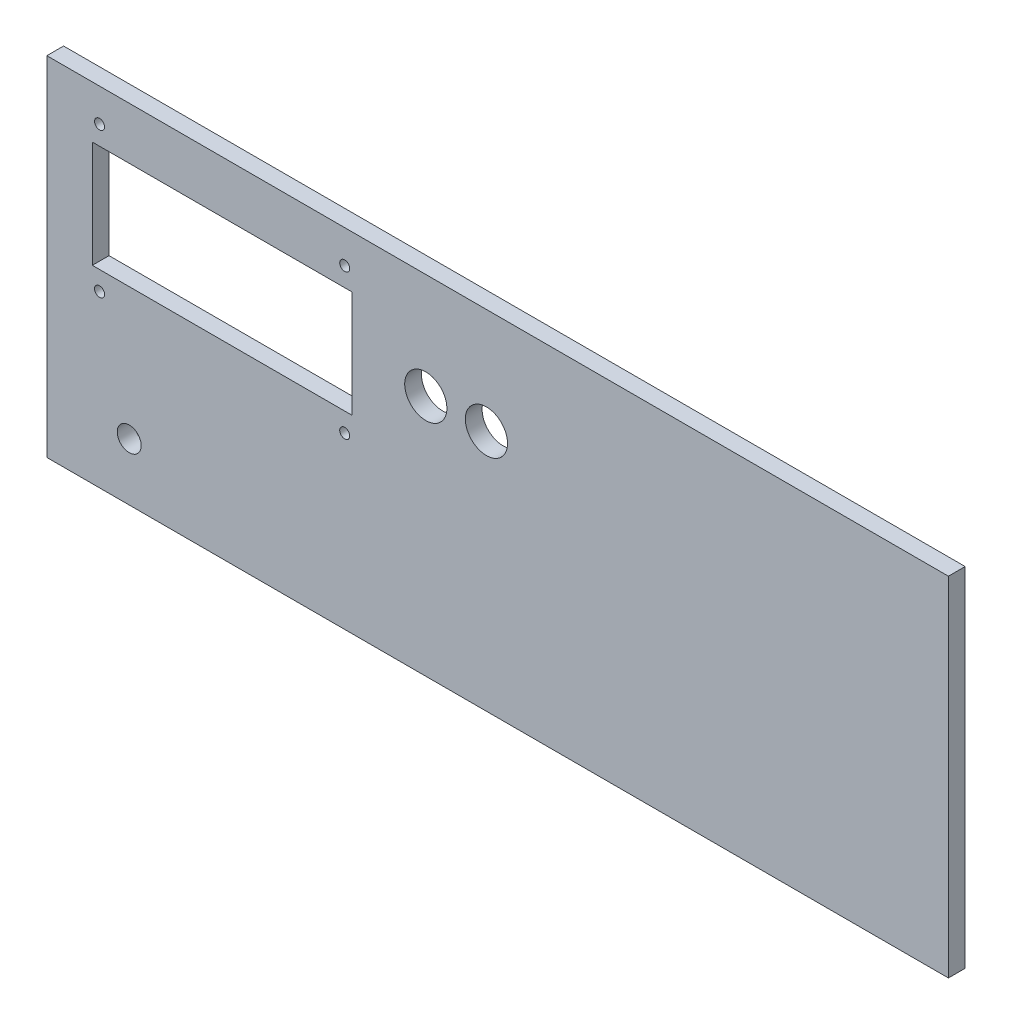
SolidWorks part; units mm, degrees
ref_plane "Front Plane" through (0, 0, 0) normal (0, 0, 1) x (1, 0, 0)
ref_plane "Top Plane" through (0, 0, 0) normal (0, 1, 0) x (1, 0, 0)
ref_plane "Right Plane" through (0, 0, 0) normal (1, 0, 0) x (0, 0, -1)
sketch "Sketch1" plane through (0, 0, 0) normal (0, 0, 1) x (1, 0, 0)
  line L0 (66.5, 92) -> (66.5, 112.25) construction
  line L1 (0, 0) -> (342, 0)
  line L2 (0, 0) -> (0, 132)
  line L3 (0, 132) -> (342, 132)
  line L4 (342, 0) -> (342, 132)
  line L13 (20, 64.5) -> (113, 119.5) construction
  line L14 (20, 119.5) -> (113, 64.5) construction
  line L15 (115.75, 92) -> (143.75, 92) construction
  line L16 (143.75, 92) -> (166.75, 92) construction
  line L17 (17.25, 71.75) -> (17.25, 21.75) construction
  line L18 (17.25, 21.75) -> (31.25, 21.75) construction
  line L19 (17.25, 71.75) -> (115.75, 71.75)
  line L20 (17.25, 71.75) -> (17.25, 112.25)
  line L21 (17.25, 112.25) -> (115.75, 112.25)
  line L22 (115.75, 71.75) -> (115.75, 112.25)
  line L23 (17.25, 71.75) -> (115.75, 112.25) construction
  line L24 (17.25, 112.25) -> (115.75, 71.75) construction
  circle A0 centre (113, 119.5) radius 1.9
  circle A1 centre (113, 64.5) radius 1.9
  circle A2 centre (20, 64.5) radius 1.9
  circle A3 centre (20, 119.5) radius 1.9
  circle A4 centre (143.75, 92) radius 8
  circle A5 centre (166.75, 92) radius 8
  circle A6 centre (31.25, 21.75) radius 4.55
  point P5 (66.5, 92)
  point P14 (66.5, 112.25)
  point P22 (66.5, 92)
  dimension "D5" = 3.8
  dimension "D6" = 3.8
  dimension "D7" = 3.8
  dimension "D8" = 3.8
  dimension "D16" = 28
  dimension "D17" = 16
  dimension "D19" = 16
  dimension "D22" = 9.1
  dimension "D1" = 132
  dimension "D2" = 342
  dimension "D3" = 55
  dimension "D4" = 93
  dimension "D9" = 66.5
  dimension "D10" = 40
  dimension "D11" = 98.5
  dimension "D12" = 40.5
  dimension "D13" = 61.2
  dimension "D14" = 17.25
  dimension "D15" = 59.4
  dimension "D18" = 23
  dimension "D20" = 50
  dimension "D21" = 14
extrude "Boss-Extrude1" add sketch "Sketch1" along normal blind 6.35
